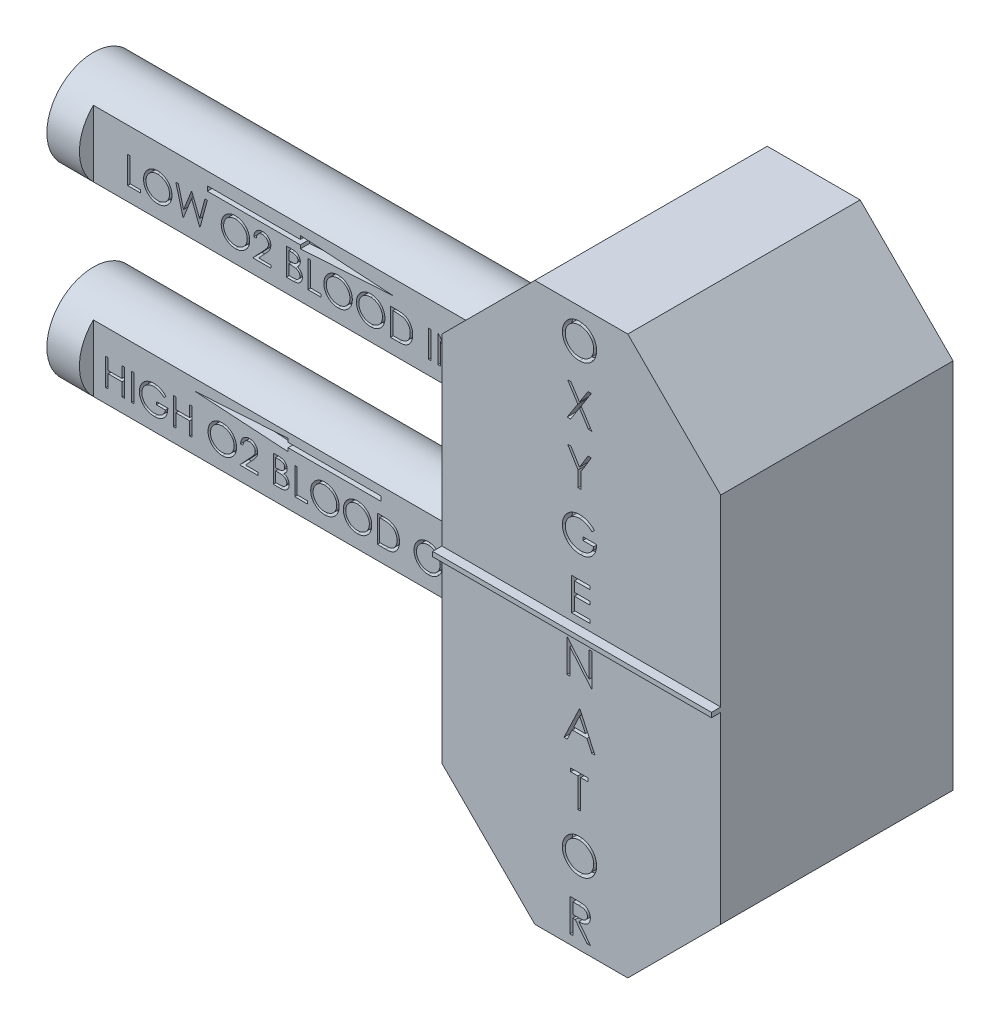
SolidWorks part; units mm, degrees
ref_plane "Front Plane" through (0, 0, 0) normal (0, 0, 1) x (1, 0, 0)
ref_plane "Top Plane" through (0, 0, 0) normal (0, 1, 0) x (1, 0, 0)
ref_plane "Right Plane" through (0, 0, 0) normal (1, 0, 0) x (0, 0, -1)
sketch "Sketch1" plane through (0, 0, 0) normal (0, 0, 1) x (1, 0, 0)
  line L0 (-15, 20) -> (-15, 30)
  line L1 (5, -30) -> (-5, -30)
  line L2 (15, -20) -> (15, 20)
  line L3 (5, 30) -> (-5, 30)
  line L4 (-15, -20) -> (-15, 20)
  line L5 (15, -30) -> (-15, 30) construction
  line L6 (15, 30) -> (-15, -30) construction
  line L7 (-15, 30) -> (-5, 30)
  line L8 (5, 30) -> (15, 30)
  line L9 (15, 30) -> (15, 20)
  line L10 (5, -30) -> (15, -30)
  line L11 (15, -30) -> (15, -20)
  line L12 (-15, -20) -> (-15, -30)
  line L13 (-15, -30) -> (-5, -30)
  point P0 (0, 0)
  dimension "D1" = 30
  dimension "D2" = 60
extrude "Boss-Extrude1" add sketch "Sketch1" along normal mid plane 25
chamfer "Chamfer1" distance 10 angle 45 4 edges at (15, -30, 0) (-15, -30, 0) (-15, 30, 0) (15, 30, 0)
sketch "Sketch3" plane through (0, 0, 12.5) normal (0, 0, 1) x (1, 0, 0)
  line L0 (-15, 0) -> (15, 0) construction
  line L1 (-15, 20) -> (-15, -20) construction
  line L2 (15, -20) -> (15, 20) construction
  line L3 (-15, 0.25) -> (15, 0.25)
  line L4 (-15, -0.25) -> (15, -0.25)
  line L5 (-15, 0.25) -> (-15, -0.25)
  line L6 (15, 0.25) -> (15, -0.25)
  dimension "D1" = 0.25
extrude "Boss-Extrude2" add sketch "Sketch3" along normal blind 1
sketch "Sketch4" plane through (0, 0, 12.5) normal (0, 0, 1) x (1, 0, 0)
  line L0 (-4.6878, 25) -> (4.2927, 25) construction
  line L1 (5, 30) -> (-5, 30) construction
  line L2 (-4.6878, 19) -> (4.2927, 19) construction
  line L3 (-4.6878, 13) -> (4.2927, 13) construction
  line L4 (-4.6878, 7) -> (4.2927, 7) construction
  line L5 (-4.6878, 1) -> (4.2927, 1) construction
  line L6 (-4.6878, -5) -> (4.2927, -5) construction
  line L7 (-4.6878, -11) -> (4.2927, -11) construction
  line L8 (-4.6878, -17) -> (4.2927, -17) construction
  line L9 (-4.6878, -23) -> (4.2927, -23) construction
  line L10 (-4.6878, -29) -> (4.2927, -29) construction
  text T0 "O"
  text T1 "X"
  text T2 "Y"
  text T3 "G"
  text T4 "E"
  text T5 "N"
  text T6 "A"
  text T7 "T"
  text T8 "O"
  text T9 "R"
  dimension "D1" = 5
  dimension "D2" = 10
extrude "Cut-Extrude2" cut sketch "Sketch4" against normal blind 1
sketch "Sketch5" plane through (-15, 0, 0) normal (-1, 0, 0) x (0, 0, 1)
  line L0 (0, 20) -> (0, -20) construction
  line L1 (12.5, 20) -> (-12.5, 20) construction
  line L2 (-12.5, -20) -> (12.5, -20) construction
  circle A0 centre (0, 10) radius 5
  circle A1 centre (0, -10) radius 5
  dimension "D1" = 10
  dimension "D2" = 10
  dimension "D4" = 10
  dimension "D3" = 10
extrude "Boss-Extrude3" add sketch "Sketch5" along normal blind 50
sketch "Sketch6" plane through (0, 0, 12.5) normal (0, 0, 1) x (1, 0, 0)
  line L0 (-15, 15) -> (-65, 15) construction
  line L1 (-18.5, -19.3467) -> (-61.5, -19.3467)
  line L2 (-18.5, -19.3467) -> (-18.5, 15)
  line L3 (-18.5, 15) -> (-61.5, 15)
  line L4 (-61.5, -19.3467) -> (-61.5, 15)
  line L5 (-18.5, -19.3467) -> (-61.5, 15) construction
  line L6 (-18.5, 15) -> (-61.5, -19.3467) construction
  line L7 (-65, 15) -> (-65, 5) construction
  line L8 (-15, 20) -> (-15, 0.25) construction
  point P0 (-40, -2.1733)
  point P7 (-39.7243, 0)
  dimension "D1" = 3.5
  dimension "D2" = 3.5
extrude "Cut-Extrude3" cut sketch "Sketch6" against normal blind 9
sketch "Sketch8" plane through (0, 0, 3.5) normal (0, 0, 1) x (1, 0, 0)
  line L0 (-61.5, 7.9293) -> (-18.5, 7.9293) construction
  line L1 (-61.5, 6.4293) -> (-61.5, 13.5707) construction
  line L2 (-18.5, 6.4293) -> (-18.5, 13.5707) construction
  line L3 (-61.5, -12.0707) -> (-18.5, -12.0707) construction
  line L4 (-61.5, -13.5707) -> (-61.5, -6.4293) construction
  line L5 (-18.5, -6.4293) -> (-18.5, -13.5707) construction
  line L6 (-61.5, 6.4293) -> (-18.5, 6.4293) construction
  line L7 (-61.5, -13.5707) -> (-18.5, -13.5707) construction
  line L8 (-49.2323, 12.1957) -> (-49.2323, 11.6957)
  line L9 (-49.2323, 11.6957) -> (-39.2323, 11.6957)
  line L10 (-39.2323, 11.6957) -> (-39.2323, 11.3207)
  line L11 (-39.2323, 11.3207) -> (-29.2323, 11.9457)
  line L12 (-29.2323, 11.9457) -> (-39.2323, 12.5707)
  line L13 (-30.5514, -7.6143) -> (-50.5514, -7.6143) construction
  line L14 (-39.2323, 12.5707) -> (-39.2323, 12.1957)
  line L15 (-39.2323, 12.1957) -> (-49.2323, 12.1957)
  line L16 (-49.657, 11.9457) -> (-34.7403, 11.9457) construction
  line L17 (-30.5514, -7.8643) -> (-30.5514, -7.3643)
  line L18 (-30.5514, -7.3643) -> (-40.5514, -7.3643)
  line L19 (-40.5514, -7.3643) -> (-40.5514, -6.9893)
  line L20 (-40.5514, -6.9893) -> (-50.5514, -7.6143)
  line L21 (-50.5514, -7.6143) -> (-40.5514, -8.2393)
  line L22 (-40.5514, -8.2393) -> (-40.5514, -7.8643)
  line L23 (-40.5514, -7.8643) -> (-30.5514, -7.8643)
  text T0 "LOW O2 BLOOD IN" font "Century Gothic" height in points 11
  text T1 "HIGH O2 BLOOD OUT" font "Century Gothic" height in points 11
  dimension "D1" = 1.5
  dimension "D2" = 1.5
  dimension "D3" = 0.25
  dimension "D4" = 1.25
  dimension "D5" = 10
  dimension "D6" = 10
  dimension "D7" = 1.25
  dimension "D8" = 0.5
extrude "Cut-Extrude4" cut sketch "Sketch8" against normal blind 1
